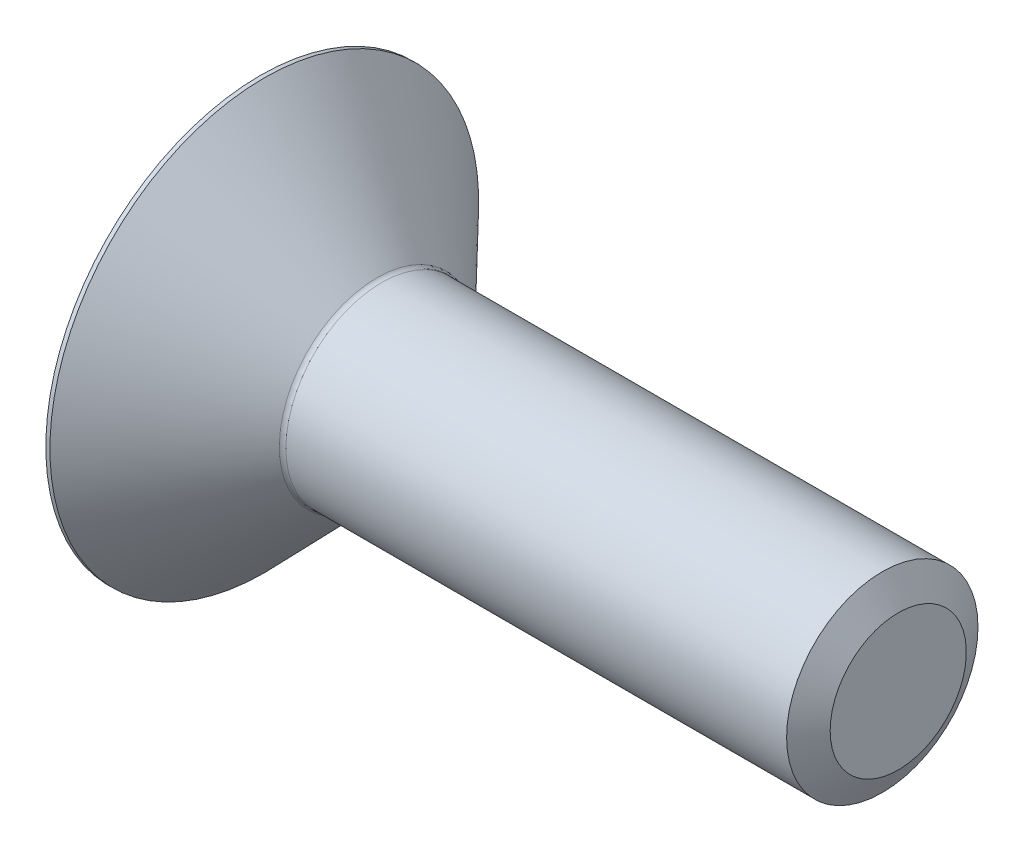
SolidWorks part; units mm, degrees
ref_plane "前视基准面" through (0, 0, 0) normal (0, 0, 1) x (1, 0, 0)
ref_plane "上视基准面" through (0, 0, 0) normal (0, 1, 0) x (1, 0, 0)
ref_plane "右视基准面" through (0, 0, 0) normal (1, 0, 0) x (0, 0, -1)
sketch "尺寸草图" plane through (0, 0, 0) normal (0, 0, 1) x (1, 0, 0)
  line L0 (0, 0) -> (10, 0) construction
  line L1 (10, 0) -> (10, 1.5) construction
  line L2 (10, 1.5) -> (9.5, 1.5) construction
  line L3 (9.5, 1.5) -> (2, 1.5) construction
  line L4 (0, 3.36) -> (1.86, 3.36) construction
  line L5 (1.86, 3.36) -> (1.96, 3.36) construction
  point P3 (10, 1.65)
  point P7 (0, 3.36)
  point P8 (0, 1.5)
  point P9 (0, 2.3)
  point P13 (0, 1)
  point P15 (1.1, 3.36)
  point P16 (1.71, 3.36)
  dimension "l" = 10
  dimension "d" = 3
  dimension "P" = 0.5
  dimension "b" = 8
  dimension "da" = 3.3
  dimension "dk" = 6.72
  dimension "ds" = 3
  dimension "e" = 2.3
  dimension "k" = 1.86
  dimension "r" = 0.1
  dimension "s" = 2
  dimension "t" = 1.1
  dimension "w" = 0.25
sketch "草图1" plane through (0, 0, 0) normal (0, 0, 1) x (1, 0, 0)
  line L0 (0, 1.5) -> (-8.0976, 1.5)
  line L1 (-8.1695, 1.5305) -> (-9.9362, 3.36)
  line L2 (-9.9362, 3.36) -> (-10, 3.36)
  line L3 (-10, 3.36) -> (-10, 0)
  line L4 (-10, 0) -> (0, 0)
  line L5 (0, 0) -> (0, 1.5)
  line L6 (0, 0) -> (-10, 0) construction
  arc A0 (-8.0976, 1.5) -> (-8.1695, 1.5305) centre (-8.0976, 1.6) cw
  point P9 (-8.14, 1.5)
  dimension "r" = 0.1
  dimension "k" = 1.86
  dimension "dk" = 6.72
  dimension "l" = 10
  dimension "D5" = 46
  dimension "d" = 3
revolve "旋转1" add sketch "草图1" angle 360 about L6
cosmetic thread "装饰螺纹线1" parameters "b"=8, "D2"=2.4
sketch "草图2" plane through (-10, 0, 0) normal (-1, 0, 0) x (0, 0, 1)
  line L0 (0, 0) -> (0, 1.5) construction
  line L1 (0, 1.1547) -> (-1, 0.5774)
  line L2 (-1, 0.5774) -> (-1, -0.5774)
  line L3 (-1, -0.5774) -> (0, -1.1547)
  line L4 (0, -1.1547) -> (1, -0.5774)
  line L5 (1, -0.5774) -> (1, 0.5774)
  line L6 (1, 0.5774) -> (0, 1.1547)
  circle A0 centre (0, 0) radius 1 construction
  point P1 (0, 1.1453)
  dimension "s" = 2
  dimension "e" = 2.3
extrude "切除-拉伸1" cut sketch "草图2" against normal blind 1.86
sketch "草图6" plane through (0, 0, 0) normal (0, 0, 1) x (1, 0, 0)
  line L0 (-8.9, 1.1547) -> (-8.2333, 0)
  line L1 (-8.2333, 0) -> (-7.84, 0)
  line L2 (-7.84, 0) -> (-7.84, 1.1547)
  line L3 (-7.84, 1.1547) -> (-8.9, 1.1547)
  line L4 (-10, 0) -> (-8.14, 0) construction
  line L5 (-10, 0) -> (-12.3, 0) construction
  dimension "D1" = 60
  dimension "t" = 1.1
  dimension "t1" = 1.86
  dimension "e-s" = 0.3
  dimension "e" = 2.3
revolve "旋转2" add sketch "草图6" angle 360 about L4
sketch "草图7" plane through (0, 0, 0) normal (0, 0, 1) x (1, 0, 0)
  line L0 (-10, 1.1547) -> (-10, 0)
  line L1 (-10, 0) -> (-9.7, 0)
  line L2 (-9.7, 0) -> (-10, 1.1547)
  line L3 (-10, 0) -> (-9.7, 0) construction
  dimension "e-s*1.1" = 0.3
revolve "切除-旋转2" cut sketch "草图7" angle 360 about L3
sketch "草图4" plane through (0, 0, 0) normal (0, 0, 1) x (1, 0, 0)
  line L0 (-0.25, 1.5) -> (0, 1.067)
  line L1 (0, -1.5) -> (0, 1.5) construction
  line L2 (0, 1.067) -> (0.25, 1.5)
  line L3 (0.25, 1.5) -> (-0.25, 1.5)
  line L4 (-0.25, 0) -> (0.25, 0) construction
  dimension "d" = 3
  dimension "p" = 0.5
revolve "切除-旋转1" cut sketch "草图4" angle 360 about L4
ref_axis "基准轴1" through (-21.1715, 0, 0) along (1, 0, 0)
pattern_linear "阵列(线性)2" [suppressed] count 16 spacing 0.5 along (-1, 0, 0) of bodies 104
